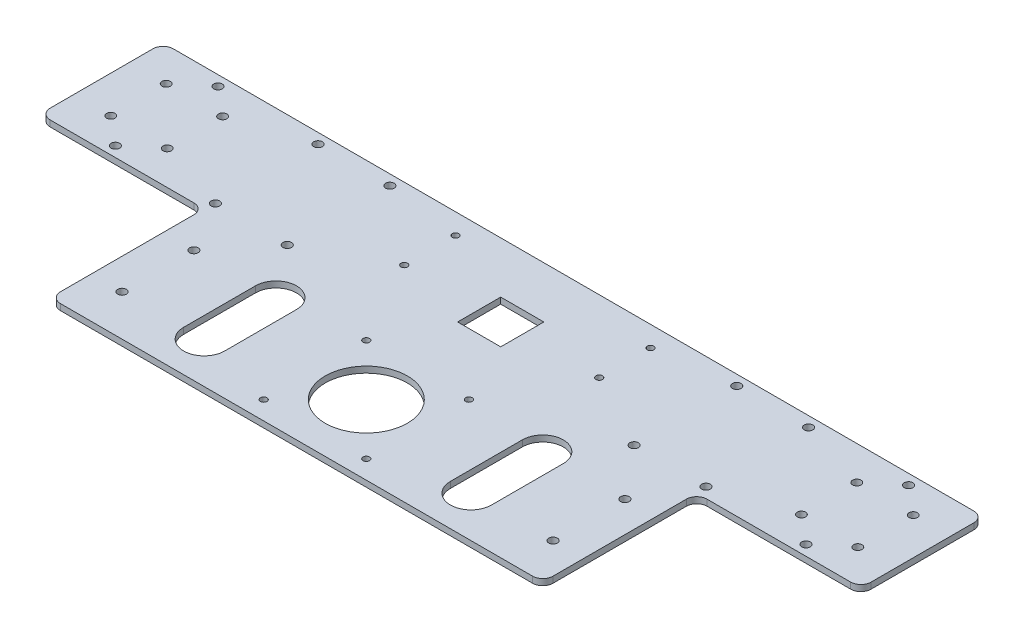
SolidWorks part; units mm, degrees
material "Thornel Mat VMA"
ref_plane "前视基准面" through (0, 0, 0) normal (0, 0, 1) x (1, 0, 0)
ref_plane "上视基准面" through (0, 0, 0) normal (0, 1, 0) x (1, 0, 0)
ref_plane "右视基准面" through (0, 0, 0) normal (1, 0, 0) x (0, 0, -1)
sketch "草图1" plane through (0, 0, 0) normal (0, 1, 0) x (1, 0, 0)
  line L0 (32.8259, -88.8718) -> (32.8259, 46.1282) construction
  line L1 (-167.1741, -13.8718) -> (232.8259, -13.8718)
  line L2 (-167.1741, -13.8718) -> (-167.1741, 46.1282)
  line L3 (-167.1741, 46.1282) -> (232.8259, 46.1282)
  line L4 (232.8259, -13.8718) -> (232.8259, 46.1282)
  line L5 (-14.6741, 36.1282) -> (80.3259, 36.1282) construction
  line L6 (-14.6741, 11.1282) -> (80.3259, 11.1282) construction
  line L7 (-87.1741, -88.8718) -> (152.8259, -88.8718)
  line L8 (-87.1741, -88.8718) -> (-87.1741, -13.8718)
  line L9 (-87.1741, -13.8718) -> (152.8259, -13.8718)
  line L10 (152.8259, -88.8718) -> (152.8259, -13.8718)
  line L11 (22.3259, 10.6282) -> (43.3259, 10.6282) construction
  line L12 (22.3259, 0.1282) -> (43.3259, 0.1282)
  line L13 (22.3259, 0.1282) -> (22.3259, 21.1282)
  line L14 (22.3259, 21.1282) -> (43.3259, 21.1282)
  line L15 (43.3259, 0.1282) -> (43.3259, 21.1282)
  line L16 (7.8259, -54.8718) -> (57.8259, -54.8718) construction
  line L17 (7.8259, -29.8718) -> (57.8259, -29.8718) construction
  line L18 (7.8259, -29.8718) -> (7.8259, -79.8718) construction
  line L19 (7.8259, -79.8718) -> (57.8259, -79.8718) construction
  line L20 (57.8259, -29.8718) -> (57.8259, -79.8718) construction
  line L21 (32.8259, 21.1282) -> (32.8259, 0.1282) construction
  line L22 (7.8259, -29.8718) -> (29.2904, -51.3362) construction
  line L23 (57.8259, -29.8718) -> (7.8259, -79.8718) construction
  line L31 (36.3615, -58.4073) -> (57.8259, -79.8718) construction
  circle A0 centre (-14.6741, 36.1282) radius 1.6
  circle A1 centre (-14.6741, 11.1282) radius 1.6
  circle A2 centre (80.3259, 11.1282) radius 1.6
  circle A3 centre (80.3259, 36.1282) radius 1.6
  circle A4 centre (7.8259, -29.8718) radius 1.6
  circle A5 centre (7.8259, -79.8718) radius 1.6
  circle A6 centre (57.8259, -79.8718) radius 1.6
  circle A7 centre (57.8259, -29.8718) radius 1.6
  circle A8 centre (32.8259, -54.8718) radius 20
  point P0 (0, 0)
  point P6 (0, -121.2547)
  point P16 (32.8259, 36.1282)
  point P19 (32.8259, 11.1282)
  point P23 (32.8259, 13.1501)
  point P30 (32.8259, -20.0664)
  point P35 (32.8259, -29.8718)
  point P44 (4.2904, -33.4073)
  point P45 (54.2904, -83.4073)
  point P46 (11.3615, -26.3362)
  point P47 (61.3615, -76.3362)
  point P48 (54.2904, -26.3362)
  point P49 (4.2904, -76.3362)
  point P50 (61.3615, -33.4073)
  point P51 (11.3615, -83.4073)
  dimension "D8" = 21
  dimension "D13" = 3.2
  dimension "D9" = 40
  dimension "D1" = 400
  dimension "D2" = 60
  dimension "D3" = 75
  dimension "D4" = 240
  dimension "D5" = 10
  dimension "D6" = 95
  dimension "D7" = 25
  dimension "D10" = 30
  dimension "D11" = 15
  dimension "D12" = 50
  dimension "D14" = 10.5
extrude "构型与裁判孔" add sketch "草图1" along normal blind 3 contours L1 L4 L3 L2 A3 L15 L12 L13 L14 A0 A1 A2 A4 A7 | L7 L10 L1 L8 A6 A5 region at (-163.1293, 0, -16.1282) region at (32.8259, 0, 16.3862)
sketch "草图2" plane through (0, 3, 0) normal (0, 1, 0) x (1, 0, 0)
  line L0 (-167.1741, 16.1282) -> (232.8259, 16.1282) construction
  line L1 (-167.1741, -13.8718) -> (-167.1741, 46.1282) construction
  line L2 (232.8259, -13.8718) -> (232.8259, 46.1282) construction
  line L3 (32.8259, 46.1282) -> (32.8259, -88.8718) construction
  line L4 (-167.1741, 46.1282) -> (232.8259, 46.1282) construction
  line L5 (-87.1741, -88.8718) -> (152.8259, -88.8718) construction
  line L6 (-149.1741, 2.6282) -> (-149.1741, 29.6282) construction
  line L7 (-121.6741, 2.6282) -> (-121.6741, 29.6282) construction
  line L8 (-149.1741, 29.6282) -> (-121.6741, 29.6282) construction
  line L9 (-51.6741, -8.8718) -> (-51.6741, 41.1282) construction
  line L10 (-135.4241, 29.6282) -> (-135.4241, 46.1282) construction
  line L11 (-135.4241, 41.1282) -> (-86.6741, 41.1282) construction
  circle A0 centre (-149.1741, 29.6282) radius 2.05
  circle A1 centre (-149.1741, 2.6282) radius 2.05
  circle A2 centre (-121.6741, 29.6282) radius 2.05
  circle A3 centre (-121.6741, 2.6282) radius 2.05
  circle A4 centre (-51.6741, 41.1282) radius 2.1
  circle A5 centre (-86.6741, 41.1282) radius 2.1
  circle A6 centre (-51.6741, -8.8718) radius 2.1
  circle A7 centre (-86.6741, -8.8718) radius 2.1
  circle A8 centre (-135.4241, 41.1282) radius 2.1
  circle A9 centre (-135.4241, -8.8718) radius 2.1
  circle A10 centre (201.0759, -8.8718) radius 2.1
  circle A11 centre (201.0759, 41.1282) radius 2.1
  circle A12 centre (152.3259, -8.8718) radius 2.1
  circle A13 centre (117.3259, -8.8718) radius 2.1
  circle A14 centre (152.3259, 41.1282) radius 2.1
  circle A15 centre (117.3259, 41.1282) radius 2.1
  circle A16 centre (187.3259, 2.6282) radius 2.05
  circle A17 centre (187.3259, 29.6282) radius 2.05
  circle A18 centre (214.8259, 2.6282) radius 2.05
  circle A19 centre (214.8259, 29.6282) radius 2.05
  point P15 (-149.1741, 16.1282)
  point P20 (-121.6741, 16.1282)
  point P25 (-51.6741, 16.1282)
  dimension "D2" = 4.1
  dimension "D4" = 5
  dimension "D5" = 4.2
  dimension "D7" = 2
  dimension "D8" = 18
  dimension "D3" = 45.5
  dimension "D1" = 27
  dimension "D6" = 70
extrude "切除-拉伸1" cut sketch "草图2" against normal through all
fillet "圆角1" radius 5 8 edges at (-87.1741, 1.5, 13.8718) (152.8259, 1.5, 13.8718) (-167.1741, 1.5, 13.8718) (-167.1741, 1.5, -46.1282) (232.8259, 1.5, -46.1282) (232.8259, 1.5, 13.8718) (152.8259, 1.5, 88.8718) (-87.1741, 1.5, 88.8718)
sketch "Sketch1" plane through (0, 0, 0) normal (0, 1, 0) x (1, 0, 0)
  line L0 (-162.1741, -13.8718) -> (-92.1741, -13.8718) construction
  line L1 (-87.1741, -83.8718) -> (-87.1741, -18.8718) construction
  line L2 (32.8259, 46.1282) -> (32.8259, -164.9495) construction
  line L3 (-162.1741, 46.1282) -> (227.8259, 46.1282) construction
  line L4 (-72.1741, -33.8718) -> (-72.1741, -68.8718) construction
  line L5 (-32.1741, -33.8718) -> (-32.1741, -68.8718) construction
  line L6 (-32.1741, -68.8718) -> (-32.1741, -33.8718) construction
  line L7 (-42.1741, -68.8718) -> (-42.1741, -33.8718)
  line L8 (-22.1741, -68.8718) -> (-22.1741, -33.8718)
  line L9 (97.8259, -68.8718) -> (97.8259, -33.8718) construction
  line L10 (107.8259, -68.8718) -> (107.8259, -33.8718)
  line L11 (87.8259, -68.8718) -> (87.8259, -33.8718)
  circle A0 centre (-72.1741, -33.8718) radius 2.1
  circle A1 centre (-72.1741, -68.8718) radius 2.1
  circle A2 centre (137.8259, -68.8718) radius 2.1
  circle A3 centre (137.8259, -33.8718) radius 2.1
  arc A4 (-42.1741, -68.8718) -> (-22.1741, -68.8718) centre (-32.1741, -68.8718) ccw
  arc A5 (-22.1741, -33.8718) -> (-42.1741, -33.8718) centre (-32.1741, -33.8718) ccw
  arc A6 (107.8259, -68.8718) -> (87.8259, -68.8718) centre (97.8259, -68.8718) cw
  arc A7 (87.8259, -33.8718) -> (107.8259, -33.8718) centre (97.8259, -33.8718) cw
  point P18 (-32.1741, -51.3718)
  point P20 (-32.1741, -51.3718)
  point P27 (97.8259, -51.3718)
  dimension "D1" = 4.2
  dimension "D2" = 20
  dimension "D3" = 35
  dimension "D4" = 15
  dimension "D5" = 15
  dimension "D7" = 10
  dimension "D6" = 40
extrude "Cut-Extrude4" cut sketch "Sketch1" along normal through all
